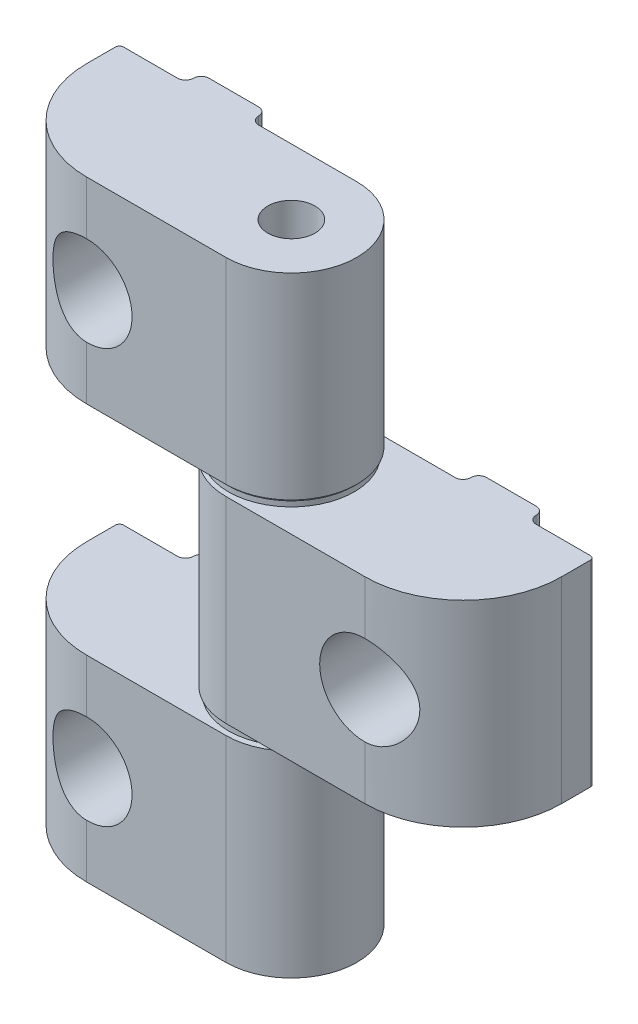
SolidWorks part; units mm, degrees
ref_plane "Front Plane" through (0, 0, 0) normal (0, 0, 1) x (1, 0, 0)
ref_plane "Top Plane" through (0, 0, 0) normal (0, 1, 0) x (1, 0, 0)
ref_plane "Right Plane" through (0, 0, 0) normal (1, 0, 0) x (0, 0, -1)
sketch "Sketch1" plane through (0, 0, 0) normal (0, 1, 0) x (1, 0, 0)
  line L0 (0, -6.35) -> (13.4874, -6.35)
  line L1 (22.6314, 6.35) -> (17.3736, 6.35)
  line L2 (23.0124, 5.969) -> (23.0124, 3.175)
  line L3 (11.049, 7.874) -> (15.8496, 7.874)
  line L6 (9.525, 6.35) -> (0, 6.35)
  circle A0 centre (0, 0) radius 6.35 construction
  arc A1 (13.4874, -6.35) -> (23.0124, 3.175) centre (13.4874, 3.175) ccw
  arc A2 (0, -6.35) -> (0, 6.35) centre (0, 0) cw
  circle A3 centre (0, 0) radius 2.286
  arc A4 (23.0124, 5.969) -> (22.6314, 6.35) centre (22.6314, 5.969) ccw
  arc A5 (9.525, 6.35) -> (10.287, 7.112) centre (9.525, 7.112) ccw
  arc A6 (10.287, 7.112) -> (11.049, 7.874) centre (11.049, 7.112) cw
  arc A7 (15.8496, 7.874) -> (16.6116, 7.112) centre (15.8496, 7.112) cw
  arc A8 (16.6116, 7.112) -> (17.3736, 6.35) centre (17.3736, 7.112) ccw
  point P11 (-6.35, 0)
  point P12 (-2.286, 0)
  point P19 (23.0124, 6.35)
  dimension "D1" = 12.7
  dimension "D4" = 4.572
  dimension "D8" = 0.381
  dimension "D7" = 0.762
  dimension "D2" = 29.3624
  dimension "D3" = 3.175
  dimension "D5" = 1.524
  dimension "D6" = 6.3246
  dimension "D9" = 6.4008
extrude "Boss-Extrude1" add sketch "Sketch1" along normal mid plane 19.05
sketch "Sketch2" plane through (0, 0, 0) normal (0, 0, 1) x (1, 0, 0)
  line L0 (0, 19.431) -> (0, -19.431)
  line L1 (0, 19.431) -> (-1.778, 19.431)
  line L2 (-1.778, 19.431) -> (-2.286, 19.431) construction
  line L3 (-2.286, 19.431) -> (-2.286, 18.923) construction
  line L4 (-2.286, 18.923) -> (-1.778, 19.431)
  line L5 (-2.286, 18.923) -> (-2.286, 10.287)
  line L6 (-2.286, 10.287) -> (-6.096, 10.287)
  line L7 (-6.096, 10.287) -> (-6.096, 9.779)
  line L8 (-6.096, 9.779) -> (-2.286, 9.779)
  line L9 (-2.286, 9.779) -> (-2.286, -9.779)
  line L10 (-2.286, -9.779) -> (-6.096, -9.779)
  line L11 (-6.096, -9.779) -> (-6.096, -10.287)
  line L12 (-6.096, -10.287) -> (-2.286, -10.287)
  line L13 (-2.286, -10.287) -> (-2.286, -18.923)
  line L14 (-2.286, -18.923) -> (-2.286, -19.431) construction
  line L15 (-2.286, -19.431) -> (-1.778, -19.431) construction
  line L16 (-1.778, -19.431) -> (0, -19.431)
  line L17 (-2.286, -18.923) -> (-1.778, -19.431)
  line L18 (-6.096, 9.779) -> (-6.096, -9.779) construction
  line L19 (-2.286, 10.287) -> (-2.286, 9.779) construction
  line L20 (-2.286, -10.287) -> (-2.286, -9.779) construction
  line L21 (0, 9.525) -> (-6.35, 9.525) construction
  dimension "D1" = 0.508
  dimension "D2" = 9.144
  dimension "D3" = 0.508
  dimension "D4" = 0.254
  dimension "D5" = 6.096
revolve "Revolve1" add sketch "Sketch2" angle 360 mid plane about L0
sketch "Sketch3" plane through (0, 0, 0) normal (0, 0, 1) x (1, 0, 0)
  line L0 (23.0124, 9.525) -> (23.0124, -9.525) construction
  line L1 (0, 0) -> (13.4366, 0) construction
  circle A0 centre (13.4366, 0) radius 2.4892
  dimension "D2" = 4.9784
  dimension "D1" = 9.5758
extrude "Cut-Extrude1" cut sketch "Sketch3" along normal through all and the other way through all
sketch "Sketch4" plane through (0, 0, -6.35) normal (0, 0, -1) x (-1, 0, 0)
  circle A0 centre (-13.4366, 0) radius 2.4892 construction
  circle A1 centre (-13.4366, 0) radius 2.4892
  circle A2 centre (-13.4366, 0) radius 4.2672
  dimension "D1" = 1.778
extrude "Boss-Extrude2" [suppressed] add sketch "Sketch4" along normal blind 2.159
sketch "Sketch5" plane through (0, 0, 6.35) normal (0, 0, 1) x (1, 0, 0)
  circle A0 centre (13.4366, 0) radius 4.3434
  dimension "D1" = 8.6868
extrude "Cut-Extrude2" cut sketch "Sketch5" against normal blind 7.1501
move or copy body "Body-Move/Copy1" bodies to move or copy 125 copy yes number of copies 1 translate (0, 20.066, 0)
move or copy body "Body-Move/Copy2" bodies to move or copy 125 copy yes number of copies 1 translate (0, -20.066, 0)
mirror "Mirror1" about plane through (0, 0, 0) normal (1, 0, 0) of bodies 126 127
delete or keep bodies "Body-Delete1" type delete bodies bodies 126 127
ref_axis "Axis1" through (13.4366, 0, -0.8001) along (0, 0, -1)
ref_plane "Plane1" through (13.4366, 0, 0) normal (1, 0, 0) x (0, 0, -1)
ref_axis "Axis2" through (-13.4366, 20.066, -0.8001) along (0, 0, -1)
ref_plane "Plane2" through (-13.4366, 0, 0) normal (1, 0, 0) x (0, 0, -1)
